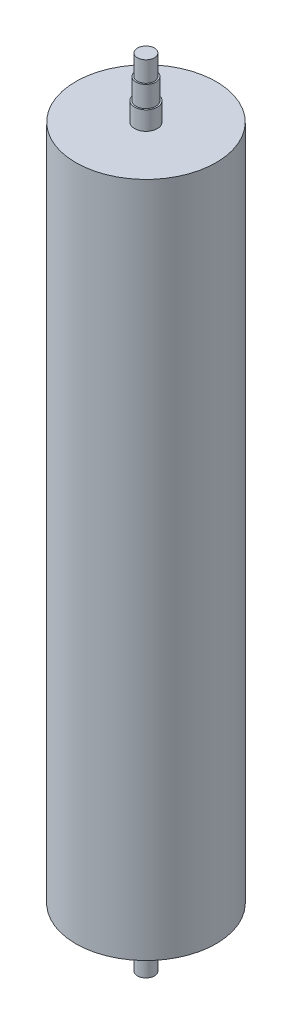
SolidWorks part; units mm, degrees
material "Stainless Steel (ferritic)"
ref_plane "Front Plane" through (0, 0, 0) normal (0, 0, 1) x (1, 0, 0)
ref_plane "Top Plane" through (0, 0, 0) normal (0, 1, 0) x (1, 0, 0)
ref_plane "Right Plane" through (0, 0, 0) normal (1, 0, 0) x (0, 0, -1)
sketch "Sketch1" plane through (0, 0, 0) normal (0, 1, 0) x (1, 0, 0)
  circle A0 centre (0, 0) radius 3.965
  circle A1 centre (0, 0) radius 3.45
  circle A2 centre (0, 0) radius 2.95
  circle A3 centre (0, 0) radius 24.5
  dimension "D1" = 7.93
  dimension "D2" = 6.9
  dimension "D3" = 5.9
  dimension "D4" = 49
extrude "Boss-Extrude8" add sketch "Sketch1" along normal blind 236 contours A3
extrude "Boss-Extrude9" add sketch "Sketch1<9>" against normal blind 14 contours A0
sketch "Sketch1<9>" plane through (0, 0, 0) normal (0, 1, 0) x (1, 0, 0) same geometry as "Sketch1"
extrude "Boss-Extrude10" add sketch "Sketch1<10>" against normal blind 6.5 from surface contours A2 region at (0, 0, 0) starting at face at (0, -14, 3.965)
sketch "Sketch1<10>" plane through (0, 0, 0) normal (0, 1, 0) x (1, 0, 0) same geometry as "Sketch1"
extrude "Boss-Extrude11" add sketch "Sketch1<11>" along normal blind 6.5 from surface contours A0 starting at face at (0, 236, 24.5)
sketch "Sketch1<11>" plane through (0, 0, 0) normal (0, 1, 0) x (1, 0, 0) same geometry as "Sketch1"
extrude "Boss-Extrude12" add sketch "Sketch1<12>" along normal blind 7.3 from surface contours A1 starting at face at (0, 242.5, 3.965)
sketch "Sketch1<12>" plane through (0, 0, 0) normal (0, 1, 0) x (1, 0, 0) same geometry as "Sketch1"
extrude "Boss-Extrude13" add sketch "Sketch1<13>" along normal blind 7.1 from surface contours A2 starting at face at (0, 249.8, 3.45)
sketch "Sketch1<13>" plane through (0, 0, 0) normal (0, 1, 0) x (1, 0, 0) same geometry as "Sketch1"
